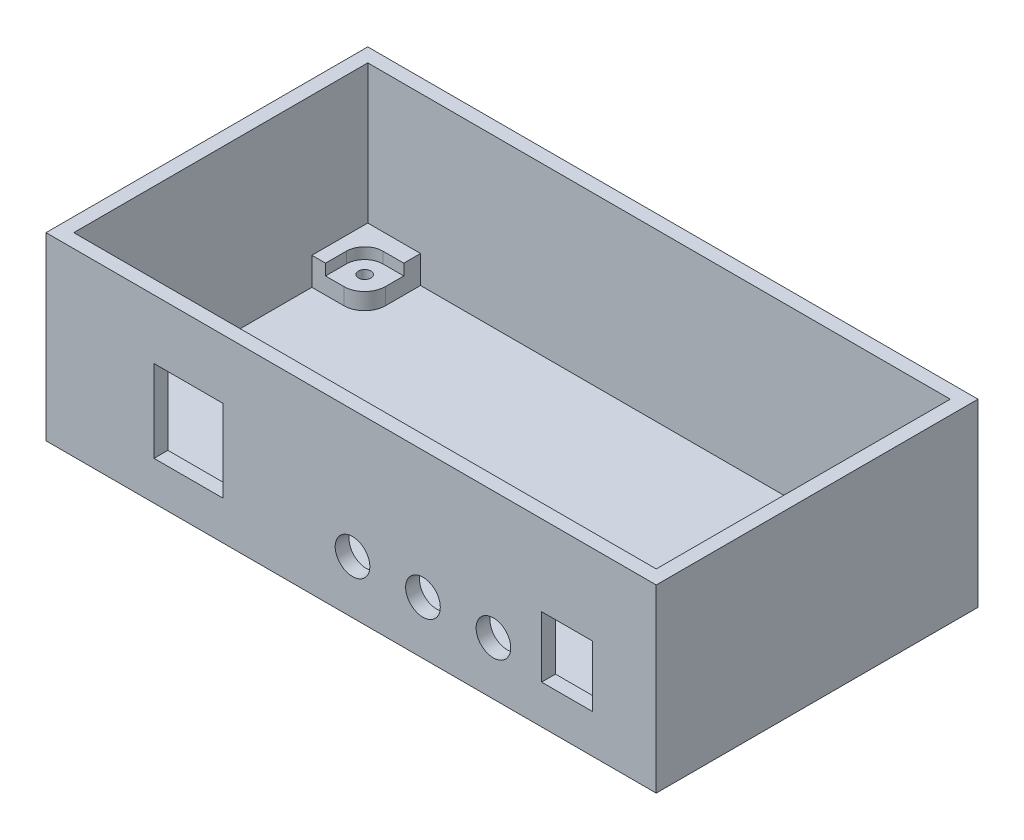
SolidWorks part; units mm, degrees
ref_plane "Front Plane" through (0, 0, 0) normal (0, 0, 1) x (1, 0, 0)
ref_plane "Top Plane" through (0, 0, 0) normal (0, 1, 0) x (1, 0, 0)
ref_plane "Right Plane" through (0, 0, 0) normal (1, 0, 0) x (0, 0, -1)
sketch "Sketch1" plane through (0, 0, 0) normal (0, 1, 0) x (1, 0, 0)
  line L1 (0, 0) -> (110, 0)
  line L2 (0, 0) -> (0, 58)
  line L3 (0, 58) -> (110, 58)
  line L4 (110, 0) -> (110, 58)
  dimension "D1" = 58
  dimension "D2" = 110
extrude "Boss-Extrude1" add sketch "Sketch1" along normal blind 2.5
sketch "Sketch2" plane through (0, 2.5, 0) normal (0, 1, 0) x (1, 0, 0)
  line L0 (110, 0) -> (110, 58) construction
  line L1 (0, 58) -> (110, 58)
  line L2 (0, 58) -> (0, 0)
  line L3 (0, 0) -> (110, 0)
  line L4 (110, 58) -> (110, 0)
  line L6 (2.5, 55.5) -> (107.5, 55.5)
  line L7 (2.5, 55.5) -> (2.5, 2.5)
  line L8 (2.5, 2.5) -> (107.5, 2.5)
  line L9 (107.5, 55.5) -> (107.5, 2.5)
  dimension "D1" = 2.5
  dimension "D2" = 2.5
  dimension "D3" = 2.5
  dimension "D4" = 2.5
extrude "Boss-Extrude2" add sketch "Sketch2" along normal blind 30
sketch "Sketch3" plane through (0, 0, 0) normal (0, 0, 1) x (1, 0, 0)
  line L0 (0, 0) -> (110, 0) construction
  line L1 (89.33, 18) -> (98.53, 18)
  line L2 (89.33, 18) -> (89.33, 7)
  line L3 (89.33, 7) -> (98.53, 7)
  line L4 (98.53, 18) -> (98.53, 7)
  line L5 (110, 32.5) -> (110, 0) construction
  line L6 (110, 9.56) -> (0, 9.56) construction
  line L7 (0, 32.5) -> (0, 0) construction
  line L9 (19.47, 21.8) -> (31.92, 21.8)
  line L10 (19.47, 21.8) -> (19.47, 7)
  line L11 (19.47, 7) -> (31.92, 7)
  line L12 (31.92, 21.8) -> (31.92, 7)
  circle A0 centre (80.65, 9.56) radius 3.125
  circle A1 centre (67.95, 9.56) radius 3.125
  circle A2 centre (55.25, 9.56) radius 3.125
  dimension "D7" = 6.25
  dimension "D1" = 9.2
  dimension "D2" = 11
  dimension "D3" = 7
  dimension "D4" = 11.47
  dimension "D5" = 9.56
  dimension "D6" = 29.35
  dimension "D9" = 12.45
  dimension "D10" = 14.8
  dimension "D11" = 7
  dimension "D12" = 78.08
  dimension "D8" = 3
extrude "Cut-Extrude1" cut sketch "Sketch3" against normal up to next
sketch "Sketch4" plane through (0, 2.5, 0) normal (0, 1, 0) x (1, 0, 0)
  line L0 (2.5, 55.5) -> (2.5, 2.5) construction
  line L1 (2.5, 2.5) -> (107.5, 2.5) construction
  line L2 (8.26, 6) -> (101.61, 6) construction
  line L3 (8.26, 6) -> (8.26, 49.18) construction
  line L4 (8.26, 49.18) -> (101.61, 49.18) construction
  line L5 (101.61, 49.18) -> (101.61, 6) construction
  circle A0 centre (8.26, 6) radius 1.1112
  circle A1 centre (101.61, 6) radius 1.1113
  circle A2 centre (8.26, 49.18) radius 1.1112
  circle A3 centre (101.61, 49.18) radius 1.1113
  dimension "D1" = 2.2225
  dimension "D5" = 2.2225
  dimension "D7" = 2.2225
  dimension "D8" = 2.2225
  dimension "D2" = 5.76
  dimension "D3" = 3.5
  dimension "D4" = 93.35
  dimension "D6" = 43.18
extrude "Cut-Extrude2" cut sketch "Sketch4" against normal through all
sketch "Sketch5" plane through (0, 2.5, 0) normal (0, 1, 0) x (1, 0, 0)
  line L0 (12.01, 49.18) -> (12.01, 55.5)
  line L1 (107.5, 55.5) -> (2.5, 55.5) construction
  line L2 (12.01, 55.5) -> (2.5, 55.5)
  line L3 (2.5, 55.5) -> (2.5, 45.43)
  line L4 (2.5, 55.5) -> (2.5, 2.5) construction
  line L5 (2.5, 45.43) -> (8.26, 45.43)
  line L6 (97.86, 49.18) -> (97.86, 55.5)
  line L7 (107.5, 55.5) -> (2.5, 55.5) construction
  line L8 (97.86, 55.5) -> (107.5, 55.5)
  line L9 (107.5, 55.5) -> (107.5, 45.43)
  line L10 (107.5, 2.5) -> (107.5, 55.5) construction
  line L11 (107.5, 45.43) -> (101.61, 45.43)
  line L12 (12.01, 6) -> (12.01, 2.5)
  line L15 (12.01, 2.5) -> (2.5, 2.5)
  line L16 (2.5, 2.5) -> (2.5, 9.75)
  line L17 (2.5, 55.5) -> (2.5, 2.5) construction
  line L18 (2.5, 9.75) -> (8.26, 9.75)
  line L19 (101.61, 9.75) -> (107.5, 9.75)
  line L22 (107.5, 9.75) -> (107.5, 2.5)
  line L23 (107.5, 2.5) -> (97.86, 2.5)
  line L24 (2.5, 2.5) -> (107.5, 2.5) construction
  line L25 (97.86, 2.5) -> (97.86, 6)
  arc A0 (8.26, 45.43) -> (12.01, 49.18) centre (8.26, 49.18) ccw
  circle A1 centre (8.26, 49.18) radius 1.1112
  arc A2 (97.86, 49.18) -> (101.61, 45.43) centre (101.61, 49.18) ccw
  circle A3 centre (101.61, 49.18) radius 1.1113
  arc A4 (12.01, 6) -> (8.26, 9.75) centre (8.26, 6) ccw
  circle A5 centre (8.26, 6) radius 1.1112
  circle A6 centre (101.61, 6) radius 1.1113
  arc A7 (101.61, 9.75) -> (97.86, 6) centre (101.61, 6) ccw
  dimension "D1" = 7.5
  dimension "D2" = 7.5
  dimension "D3" = 7.5
  dimension "D4" = 7.5
extrude "Boss-Extrude3" add sketch "Sketch5" along normal blind 5
sketch "Sketch6" plane through (0, 7.5, 0) normal (0, 1, 0) x (1, 0, 0)
  line L0 (8.26, 52.48) -> (14.5774, 52.48)
  line L1 (14.5774, 52.48) -> (14.5774, 44.4247)
  line L2 (14.5774, 44.4247) -> (4.96, 44.4247)
  line L3 (4.96, 44.4247) -> (4.96, 49.18)
  line L4 (8.26, 49.18) -> (101.61, 49.18) construction
  line L5 (54.935, 49.18) -> (54.935, 6) construction
  line L7 (101.6011, 52.6034) -> (95.2837, 52.5867)
  line L8 (95.2837, 52.5867) -> (95.305, 44.5314)
  line L9 (95.305, 44.5314) -> (104.9224, 44.5569)
  line L10 (104.9224, 44.5569) -> (104.9098, 49.3121)
  line L11 (8.26, 6) -> (101.61, 6) construction
  line L12 (54.935, 27.59) -> (2.5, 27.59) construction
  line L13 (2.5, 45.43) -> (2.5, 9.75) construction
  line L14 (104.9224, 10.6231) -> (104.9098, 5.8679)
  line L15 (95.305, 10.6486) -> (104.9224, 10.6231)
  line L16 (95.2837, 2.5933) -> (95.305, 10.6486)
  line L17 (101.6011, 2.5766) -> (95.2837, 2.5933)
  line L18 (8.26, 2.7) -> (14.5774, 2.7)
  line L19 (14.5774, 2.7) -> (14.5774, 10.7553)
  line L20 (14.5774, 10.7553) -> (4.96, 10.7553)
  line L21 (4.96, 10.7553) -> (4.96, 6)
  arc A0 (8.26, 52.48) -> (4.96, 49.18) centre (8.26, 49.18) ccw
  circle A1 centre (8.26, 49.18) radius 1.1113
  arc A2 (101.6011, 52.6034) -> (104.9098, 49.3121) centre (101.6098, 49.3034) cw
  circle A3 centre (101.6098, 49.3034) radius 1.1113
  arc A4 (101.6011, 2.5766) -> (104.9098, 5.8679) centre (101.6098, 5.8766) ccw
  arc A5 (8.26, 2.7) -> (4.96, 6) centre (8.26, 6) cw
  dimension "D1" = 6.6
extrude "Cut-Extrude3" cut sketch "Sketch6" against normal blind 2
